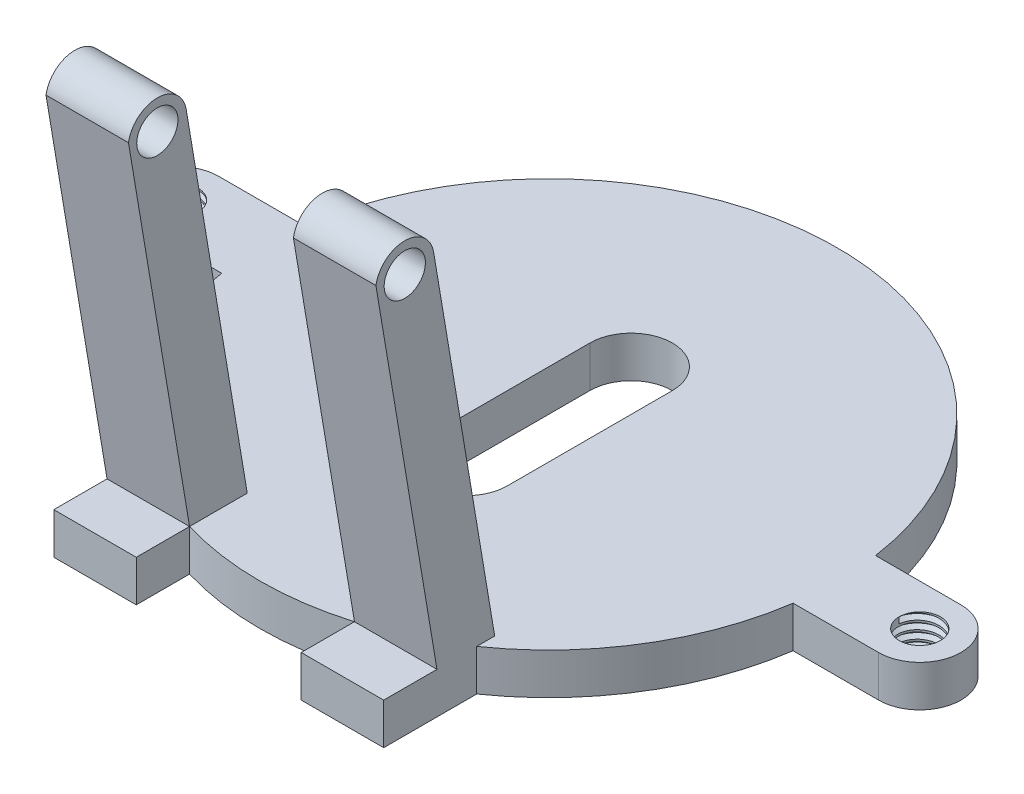
SolidWorks part; units mm, degrees
material "PVC Rigid"
ref_plane "Front Plane" through (0, 0, 0) normal (0, 0, 1) x (1, 0, 0)
ref_plane "Top Plane" through (0, 0, 0) normal (0, 1, 0) x (1, 0, 0)
ref_plane "Right Plane" through (0, 0, 0) normal (1, 0, 0) x (0, 0, -1)
sketch "Sketch1" plane through (0, 0, 0) normal (0, 1, 0) x (1, 0, 0)
  circle A0 centre (0, 0) radius 44.45
  dimension "D1" = 88.9
extrude "Boss-Extrude1" add sketch "Sketch1" along normal blind 6.35
sketch "Sketch2" plane through (0, 6.35, 0) normal (0, 1, 0) x (1, 0, 0)
  line L0 (0, 0) -> (42.672, 0) construction
  line L1 (42.672, 0) -> (42.672, 6.35)
  line L2 (42.672, 6.35) -> (57.15, 6.35)
  line L3 (57.15, -6.35) -> (42.672, -6.35)
  line L4 (42.672, -6.35) -> (42.672, 0)
  arc A0 (57.15, 6.35) -> (57.15, -6.35) centre (57.15, 0) cw
  circle A1 centre (57.15, 0) radius 3.175
  dimension "D4" = 6.35
  dimension "D1" = 6.35
  dimension "D2" = 42.672
  dimension "D3" = 14.478
extrude "Boss-Extrude2" add sketch "Sketch2" against normal up to surface (6.35 mm away) up to face at (0, 0, 44.45)
thread "Thread2" pitch 1.27 method cut profile "Thread Profile2" start angle 0, offset 0, length 10, pitch 1.27, diameter 6.35
ref_plane "Plane2" through (53.975, 6.35, 0) normal (0, 0, 1) x (-1, 0, 0)
sketch "Thread Profile2" plane through (53.975, 6.35, 0) normal (0, 0, 1) x (-1, 0, 0)
  line L0 (0, 0) -> (0, 1.27) construction
  line L1 (0, 0) -> (0.6874, 0.3969)
  line L2 (0.6874, 0.3969) -> (0.6874, 0.5556)
  line L3 (0.6874, 0.5556) -> (0, 0.9525)
  line L4 (0.6874, 0.4762) -> (0, 0.4762) construction
  line L11 (0, 0) -> (0, 0.9525)
  point P2 (0, 0)
  dimension "Pitch" = 1.27
  dimension "Profile_Angle" = 60
  dimension "Profile_Land" = 0.1588
  dimension "Profile_Height" = 0.6874
mirror "Mirror1" about plane through (0, 0, 0) normal (1, 0, 0) of "Boss-Extrude2", "Thread2"
sketch "Sketch7" plane through (0, 0, 0) normal (0, 1, 0) x (1, 0, 0)
  line L0 (0, 0) -> (43.9941, 0) construction
  line L1 (43.9941, 0) -> (43.9941, -50.8) construction
  line L2 (43.9941, -50.8) -> (-43.9941, -50.8) construction
  line L3 (-43.9941, -50.8) -> (-43.9941, 0) construction
  line L4 (-43.9941, 0) -> (0, 0) construction
  line L5 (-43.9941, 6.35) -> (-43.9941, -6.35) construction
  line L6 (-25.4, 0) -> (25.4, 0) construction
  line L7 (-25.4, 0) -> (-25.4, -50.8) construction
  line L8 (25.4, 0) -> (25.4, -50.8) construction
  line L9 (-25.4, -25.4) -> (-25.4, -50.8)
  line L10 (-25.4, -50.8) -> (-12.7, -50.8)
  line L11 (25.4, -50.8) -> (25.4, -25.4)
  line L12 (-12.7, -50.8) -> (-12.7, -38.1)
  line L13 (-12.7, -38.1) -> (12.7, -38.1)
  line L14 (12.7, -38.1) -> (12.7, -50.8)
  line L15 (12.7, -50.8) -> (25.4, -50.8)
  line L16 (-25.4, -25.4) -> (25.4, -25.4)
  arc A0 (-43.9941, -6.35) -> (43.9941, -6.35) centre (0, 0) ccw construction
  point P16 (0, 0)
  dimension "D1" = 50.8
  dimension "D2" = 50.8
  dimension "D3" = 25.4
  dimension "D4" = 12.7
extrude "Boss-Extrude3" add sketch "Sketch7" along normal up to surface (6.35 mm away) up to face at (0, 6.35, 0)
sketch3d "3DSketch2"
  line L1 (-12.7, 6.35, 42.5971) -> (-12.7, 6.35, 33.7071)
  line L2 (-12.7, 6.35, 42.5971) -> (-25.4, 6.35, 42.5971)
  line L3 (-25.4, 6.35, 42.5971) -> (-25.4, 6.35, 33.7071)
  line L4 (-12.7, 6.35, 33.7071) -> (-25.4, 6.35, 33.7071)
  line L5 (-12.7, 6.35, 38.1521) -> (-25.4, 6.35, 38.1521) construction
  line L6 (-19.05, 6.35, 42.5971) -> (-19.05, 6.35, 50.8) construction
  line L7 (-25.4, 6.35, 50.8) -> (-12.7, 6.35, 50.8) construction
  line L8 (-19.05, 6.35, 46.6985) -> (-19.05, 57.15, 46.6985) construction
  line L9 (-19.05, 57.15, 46.6985) -> (-19.05, 6.35, 38.1521) construction
  line L10 (-25.4, 6.35, 36.478) -> (-25.4, 6.35, 50.8) construction
  line L11 (-19.05, 6.35, 42.5971) -> (-19.05, 6.35, 33.7071) construction
  point P23 (-19.05, 6.35, 38.1521)
  dimension "D1" = 50.8
  dimension "D3" = 8.89
sketch3d "3DSketch3"
  line L2 (-19.05, 57.15, 46.6985) -> (-19.05, 6.35, 46.6985) construction
  line L4 (-19.05, 6.35, 38.1521) -> (-19.05, 57.15, 46.6985)
  line L5 (-12.7, 6.35, 38.1521) -> (-25.4, 6.35, 38.1521) construction
sweep "Sweep1" add profiles "3DSketch2" path "3DSketch3"
sketch "Sketch9" plane through (-25.4, 0, 0) normal (-1, 0, 0) x (0, 0, 1)
  line L0 (42.2535, 57.15) -> (51.1435, 57.15)
  line L3 (42.2535, 57.15) -> (43.1082, 62.23)
  line L4 (51.9982, 62.23) -> (51.1435, 57.15)
  line L7 (51.1435, 57.15) -> (42.2535, 57.15) construction
  line L8 (42.5971, 6.35) -> (51.1435, 57.15) construction
  line L9 (33.7071, 6.35) -> (42.2535, 57.15) construction
  arc A0 (43.1082, 62.23) -> (51.9982, 62.23) centre (47.5532, 61.4822) cw
  circle A1 centre (47.5532, 61.4822) radius 3.175
  dimension "D2" = 6.35
  dimension "D1" = 5.08
extrude "Boss-Extrude4" add sketch "Sketch9" against normal up to surface (12.7 mm away) up to face at (-12.7, 31.75, 42.4253)
mirror "Mirror2" about plane through (0, 0, 0) normal (1, 0, 0) of "Boss-Extrude4", "Sweep1"
sketch "Sketch10" plane through (0, 6.35, 0) normal (0, 1, 0) x (1, 0, 0)
  line L0 (0, 12.7) -> (0, -12.7) construction
  line L1 (6.35, 12.7) -> (6.35, -12.7)
  line L2 (-6.35, 12.7) -> (-6.35, -12.7)
  arc A0 (6.35, 12.7) -> (-6.35, 12.7) centre (0, 12.7) ccw
  arc A1 (-6.35, -12.7) -> (6.35, -12.7) centre (0, -12.7) ccw
  point P2 (0, 0)
  dimension "D1" = 6.35
  dimension "D2" = 25.4
extrude "Cut-Extrude1" cut sketch "Sketch10" against normal up to surface (6.35 mm away) up to face at (0, 0, 20.5603)
sketch "Sketch11" plane through (0, 0, 0) normal (1, 0, 0) x (0, 0, -1)
  line L0 (0, 0) -> (0, 6.35) construction
  line L1 (0, 6.35) -> (0, 61.4822) construction
  line L2 (0, 61.4822) -> (-47.5532, 61.4822) construction
  line L4 (0, 61.4822) -> (0, 86.8822) construction
  line L5 (0, 86.8822) -> (-165.1, 86.8822) construction
  dimension "D1" = 165.1
  dimension "D2" = 25.4
